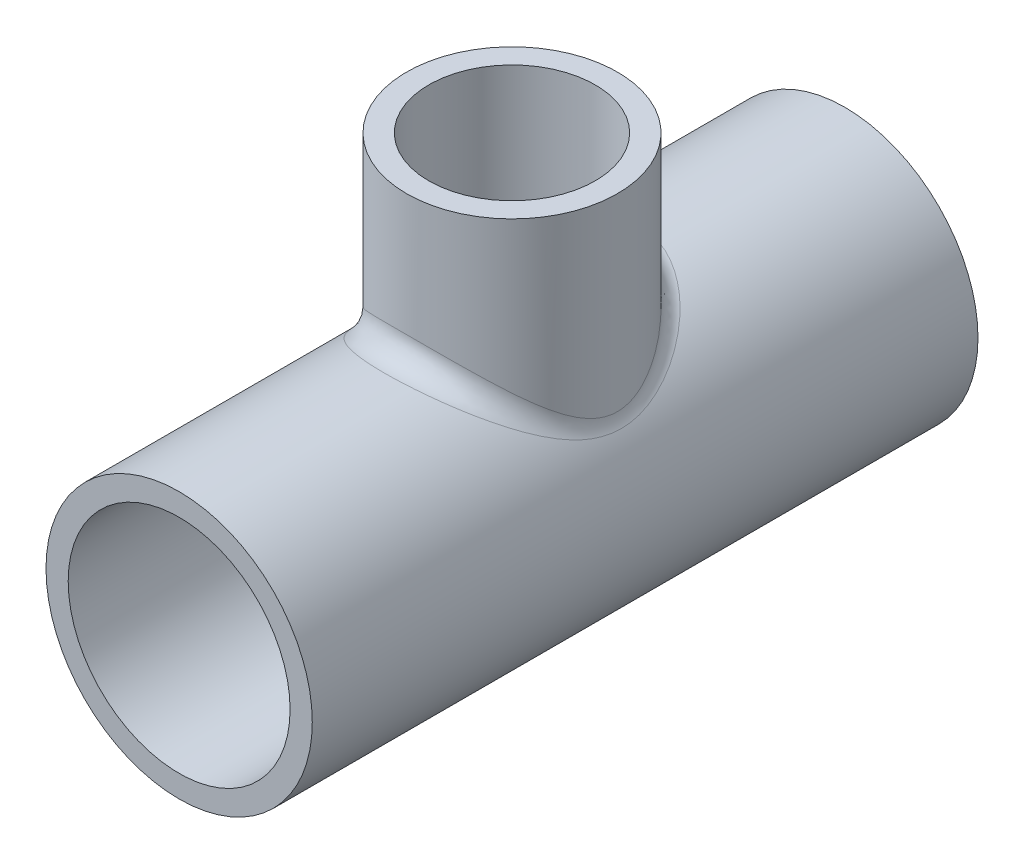
SolidWorks part; units mm, degrees
material "PVC 0.007 Plasticized"
ref_plane "Front Plane" through (0, 0, 0) normal (0, 0, 1) x (1, 0, 0)
ref_plane "Top Plane" through (0, 0, 0) normal (0, 1, 0) x (1, 0, 0)
ref_plane "Right Plane" through (0, 0, 0) normal (1, 0, 0) x (0, 0, -1)
sketch "Sketch1" plane through (0, 0, 0) normal (0, 0, 1) x (1, 0, 0)
  circle A0 centre (0, 0) radius 10
  circle A1 centre (0, 0) radius 12
  dimension "D1" = 20
  dimension "D2" = 2
extrude "Boss-Extrude1" add sketch "Sketch1" against normal blind 60 contours A1 A0 region at (-11.6606, 0, 0)
sketch "Sketch2" plane through (0, 0, 0) normal (0, 1, 0) x (1, 0, 0)
  line L0 (0, 0) -> (0, 60) construction
  line L1 (10, 60) -> (-10, 60) construction
  line L2 (-12, 30) -> (12, 30) construction
  line L3 (-12, 60) -> (-12, 0) construction
  line L4 (12, 0) -> (12, 60) construction
  circle A1 centre (0, 30) radius 7.5
  circle A2 centre (0, 30) radius 9.5
  dimension "D1" = 15
  dimension "D2" = 2
extrude "Boss-Extrude2" add sketch "Sketch2" along normal blind 25 and the other way up to surface other way up to face at (12, 0, -60)
sketch "Sketch3" plane through (0, 0, 0) normal (0, 1, 0) x (1, 0, 0)
  circle A0 centre (0, 30) radius 7.5 construction
  circle A1 centre (0, 30) radius 7.5
extrude "Cut-Extrude1" cut sketch "Sketch3" along normal blind 20
sketch "Sketch4" plane through (0, 0, 0) normal (0, 0, 1) x (1, 0, 0)
  circle A0 centre (0, 0) radius 10 construction
  circle A1 centre (0, 0) radius 10
extrude "Cut-Extrude2" cut sketch "Sketch4" against normal through all both and the other way through all
fillet "Fillet1" radius 2 1 edges at (-1.2635, 11.9333, -39.4156)
